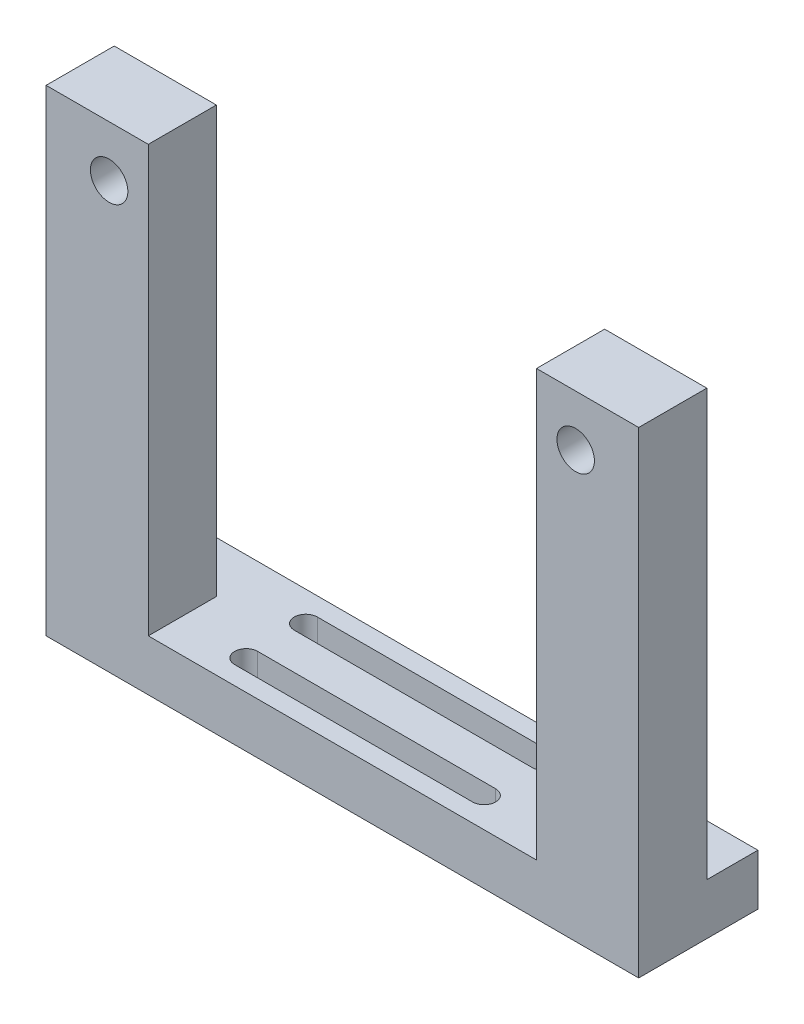
SolidWorks part; units mm, degrees
ref_plane "前视基准面" through (0, 0, 0) normal (0, 0, 1) x (1, 0, 0)
ref_plane "上视基准面" through (0, 0, 0) normal (0, 1, 0) x (1, 0, 0)
ref_plane "右视基准面" through (0, 0, 0) normal (1, 0, 0) x (0, 0, -1)
other "Configuration Table"
sketch "草图1" plane through (0, 0, 0) normal (0, 0, 1) x (1, 0, 0)
  line L0 (-17.4, -11) -> (17.4, -11)
  line L1 (-11.4, 14) -> (11.4, 14)
  line L2 (-11.4, 14) -> (-11.4, -14)
  line L3 (-11.4, -14) -> (11.4, -14)
  line L4 (11.4, 14) -> (11.4, -14)
  line L5 (-11.4, 14) -> (11.4, -14) construction
  line L6 (-11.4, -14) -> (11.4, 14) construction
  line L7 (-17.4, 14) -> (17.4, 14)
  line L8 (-17.4, 14) -> (-17.4, -14)
  line L9 (-17.4, -14) -> (17.4, -14)
  line L10 (17.4, 14) -> (17.4, -14)
  line L11 (-17.4, 14) -> (17.4, -14) construction
  line L12 (-17.4, -14) -> (17.4, 14) construction
  point P0 (0, 0)
  point P5 (0, 0)
  dimension "D1" = 22.8
  dimension "D2" = 28
  dimension "D3" = 6
  dimension "D4" = 3
extrude "凸台-拉伸1" add sketch "草图1" along normal blind 4 contours L7 L8 L0 L2 | L8 L9 L2 L0 | L4 L0 L2 L3 | L10 L0 L4 L9 | L10 L7 L4 L0 region at (-14.4, 1.5, 0) region at (-14.4, -12.5, 0) region at (0, -12.5, 0) region at (14.4, 1.5, 0) region at (14.4, -12.5, 0)
sketch "草图3" plane through (0, 0, 0) normal (0, 0, -1) x (-1, 0, 0)
  line L0 (0, 15.0676) -> (0, -5.1843) construction
  line L4 (-11.4, 14) -> (-17.4, 14) construction
  circle A0 centre (-13.7, 11) radius 1.1
  circle A1 centre (13.7, 11) radius 1.1
  dimension "D1" = 2.2
  dimension "D2" = 2.2
  dimension "D3" = 27.4
  dimension "D4" = 3
extrude "切除-拉伸2" cut sketch "草图3" against normal through all
sketch "草图4" plane through (0, -14, 0) normal (0, -1, 0) x (1, 0, 0)
  line L1 (-17.4, 0) -> (17.4, 0)
  line L2 (-17.4, 0) -> (-17.4, -3)
  line L3 (-17.4, -3) -> (17.4, -3)
  line L4 (17.4, 0) -> (17.4, -3)
  point P5 (16.4, 0)
  dimension "D1" = 3
extrude "凸台-拉伸2" add sketch "草图4" against normal blind 3
sketch "草图5" plane through (0, -11, 0) normal (0, 1, 0) x (1, 0, 0)
  line L1 (6.5715, 1.25) -> (-7.4, 1.25) construction
  line L2 (6.5715, 0.575) -> (-7.4, 0.575)
  line L3 (6.5715, 1.925) -> (-7.4, 1.925)
  line L4 (-7.4, -2.25) -> (6.5715, -2.25) construction
  line L5 (-7.4, -1.575) -> (6.5715, -1.575)
  line L6 (-7.4, -2.925) -> (6.5715, -2.925)
  line L7 (-10.6986, -0.5) -> (12.8691, -0.5) construction
  line L8 (-17.4, 3) -> (17.4, 3) construction
  line L9 (-11.4, -4) -> (11.4, -4) construction
  line L10 (-11.4, -4) -> (-11.4, 0) construction
  line L11 (-7.4, 1.25) -> (-7.4, -0.5) construction
  line L12 (-7.4, 1.25) -> (-7.4, 3) construction
  arc A0 (6.5715, 0.575) -> (6.5715, 1.925) centre (6.5715, 1.25) ccw
  arc A1 (-7.4, 1.925) -> (-7.4, 0.575) centre (-7.4, 1.25) ccw
  arc A2 (-7.4, -1.575) -> (-7.4, -2.925) centre (-7.4, -2.25) ccw
  arc A3 (6.5715, -2.925) -> (6.5715, -1.575) centre (6.5715, -2.25) ccw
  spline S0 degree 3 poles (-1.0397, 0.6928) (-1.0178, 0.6933) (-0.9746, 0.6944) (-0.9112, 0.7034) (-0.8505, 0.718) (-0.7925, 0.7386) (-0.7372, 0.7651) (-0.6849, 0.7981) (-0.6348, 0.8362) (-0.5882, 0.8801) (-0.5454, 0.9285) (-0.5082, 0.9813) (-0.4766, 1.0378) (-0.4505, 1.0979) (-0.4304, 1.1619) (-0.4163, 1.2296) (-0.4078, 1.301) (-0.4067, 1.3499) (-0.4061, 1.3749) knots 0 0 0 0 0.063047 0.124207 0.183658 0.242406 0.300722 0.359831 0.419929 0.481518 0.543486 0.605372 0.666977 0.729505 0.793452 0.859465 0.928135 1 1 1 1 construction
  point P1 (-0.4143, 1.25)
  point P8 (-0.4143, -2.25)
  dimension "D1" = 1.35
  dimension "D3" = 4
extrude "切除-拉伸3" cut sketch "草图5" against normal through all
